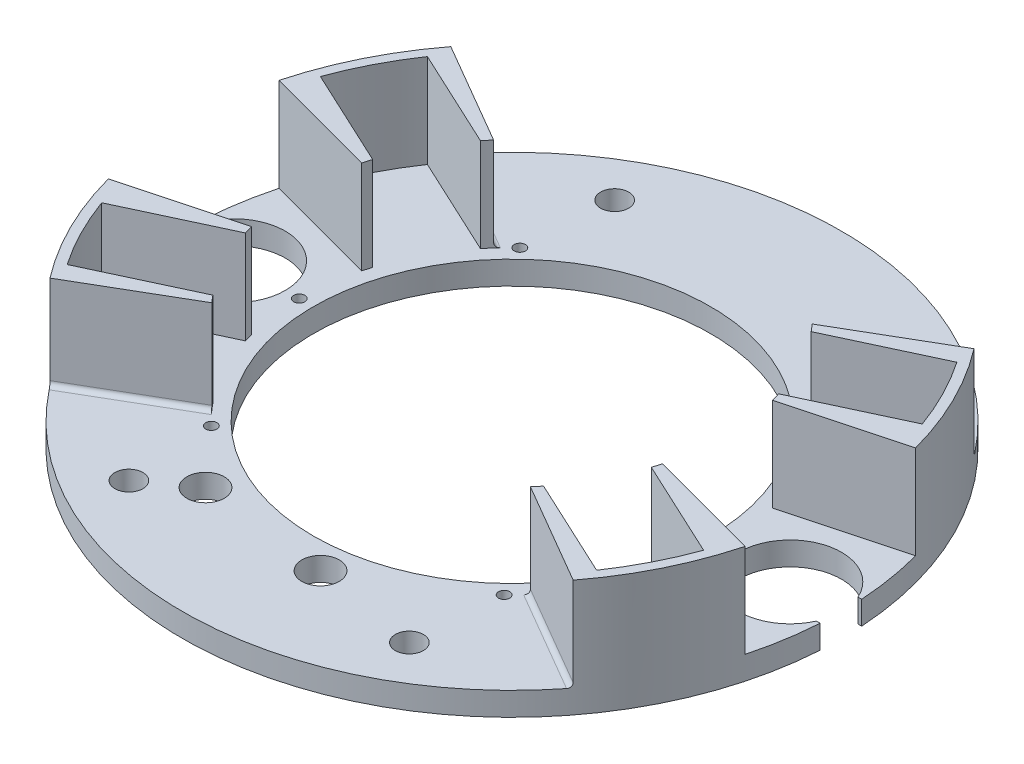
SolidWorks part; units mm, degrees
ref_plane "Front Plane" through (0, 0, 0) normal (0, 0, 1) x (1, 0, 0)
ref_plane "Top Plane" through (0, 0, 0) normal (0, 1, 0) x (1, 0, 0)
ref_plane "Right Plane" through (0, 0, 0) normal (1, 0, 0) x (0, 0, -1)
sketch "Sketch1" plane through (0, 0, 0) normal (0, 1, 0) x (1, 0, 0)
  circle A0 centre (0, 0) radius 53.975
  circle A1 centre (0, 0) radius 89.535
  dimension "D1" = 107.95
  dimension "D2" = 35.56
extrude "Base " add sketch "Sketch1" along normal blind 6.35
sketch "Sketch2" plane through (0, 6.35, 0) normal (0, 1, 0) x (1, 0, 0)
  line L0 (0, 0) -> (0, 53.975) construction
  line L1 (0, 0) -> (75.565, 0) construction
  line L2 (88.3404, 5.6524) -> (89.3564, 5.6524)
  line L3 (88.3404, -5.6524) -> (89.3564, -5.6524)
  circle A0 centre (0, 0) radius 53.975 construction
  circle A1 centre (0, 0) radius 89.535 construction
  circle A2 centre (0, 0) radius 89.535
  circle A3 centre (0, 0) radius 53.975
  arc A4 (88.3404, 5.6524) -> (88.3404, -5.6524) centre (75.565, 0) ccw
  dimension "D2" = 27.94
  dimension "D1" = 1.016
extrude "Noce Cone Pyros " cut sketch "Sketch2" against normal up to surface (6.35 mm away) contours A4 region at (75.6474, 6.35, 0) up to face at (0, 0, 89.535)
mirror "Nose Cone Pyro mirror " about plane through (0, 0, 0) normal (1, 0, 0) of "Noce Cone Pyros "
sketch "Sketch3" plane through (0, 6.35, 0) normal (0, 1, 0) x (1, 0, 0)
  line L0 (0, 0) -> (0, 53.975) construction
  line L1 (52.1358, 13.9698) -> (86.4842, 23.1734)
  line L2 (0, 0) -> (53.975, 0) construction
  line L3 (44.9222, 36.347) -> (74.256, 50.0256)
  line L4 (43.2815, 38.286) -> (71.074, 54.4518)
  line L5 (54.8014, 17.1318) -> (81.7661, 29.7057)
  circle A0 centre (0, 0) radius 53.975 construction
  circle A1 centre (0, 0) radius 89.535 construction
  circle A2 centre (0, 0) radius 89.535
  circle A3 centre (0, 0) radius 53.975
  circle A4 centre (0, 0) radius 86.995
  circle A5 centre (0, 0) radius 57.785
  arc A7 (-89.535, 0) -> (89.535, 0) centre (0, 0) ccw construction
  dimension "D1" = 15
  dimension "D2" = 90
  dimension "D3" = 21.59
  dimension "D5" = 5.185
  dimension "D7" = 10
  dimension "D8" = 2.54
  dimension "D4" = 2.54
  dimension "D6" = 3.81
extrude "Battery 1 Holder " add sketch "Sketch3" along normal blind 25.4 contours A4 L3 L4 | A5 L3 A4 L4 | A4 L1 L3 | L1 A4 L5 region at (71.5669, 6.35, -21.982) region at (79.9182, 6.35, -36.5031) region at (58.8023, 6.35, -44.9995) region at (71.5588, 6.35, -51.6651)
mirror "Batery 2 Holder " about plane through (0, 0, 0) normal (0, 0, 1) of "Battery 1 Holder "
mirror "Battery 3 Holder " about plane through (0, 0, 0) normal (1, 0, 0) of "Battery 1 Holder "
mirror "Battery 4 Holder " about plane through (0, 0, 0) normal (1, 0, 0) of "Batery 2 Holder "
sketch "Sketch4" plane through (0, 6.35, 0) normal (0, 1, 0) x (1, 0, 0)
  line L0 (0, 0) -> (0, -63.5) construction
  line L1 (0, 0) -> (38.1, 65.9911) construction
  circle A0 centre (0, 0) radius 53.975 construction
  circle A1 centre (38.1, 65.9911) radius 3.81
  dimension "D3" = 7.62
  dimension "D1" = 30
  dimension "D2" = 76.2
extrude "Bolt Hole " cut sketch "Sketch4" against normal up to surface (6.35 mm away) up to face at (0, 0, 53.975)
mirror "Bolt Hole 2 " about plane through (0, 0, 0) normal (0, 0, 1) of "Bolt Hole "
mirror "Bolt Hole 3 " about plane through (0, 0, 0) normal (1, 0, 0) of "Bolt Hole "
mirror "Bolt Hole 4 " about plane through (0, 0, 0) normal (1, 0, 0) of "Bolt Hole 2 "
sketch "Sketch11" plane through (0, 0, 0) normal (0, -1, 0) x (1, 0, 0)
  line L0 (0, 0) -> (9.1284, 61.146) construction
  line L1 (0, 0) -> (-26.0597, 57.2093) construction
  line L2 (0, 0) -> (-61.595, 0) construction
  circle A0 centre (9.1284, 61.146) radius 5.08
  circle A1 centre (-26.0597, 57.2093) radius 5.08
  arc A2 (-88.3404, -5.6524) -> (-88.3404, 5.6524) centre (-75.565, 0) ccw construction
  dimension "D4" = 10.16
  dimension "D5" = 10.16
  dimension "D1" = 62.865
  dimension "D2" = 61.8236
  dimension "D3" = 35.4076
  dimension "D6" = 65.51
extrude "Cut-Extrude2" cut sketch "Sketch11" against normal up to surface (6.35 mm away) up to face at (-38.1, 6.35, 62.1811)
sketch "Sketch13" plane through (0, 0, 0) normal (0, -1, 0) x (1, 0, 0)
  line L0 (0, 0) -> (0, 41.91) construction
  line L1 (0, 41.91) -> (39.7764, 41.91) construction
  line L2 (0, 41.91) -> (-39.7764, 41.91) construction
  circle A2 centre (39.7764, 41.91) radius 3.175
  circle A3 centre (-39.7764, 41.91) radius 3.175
  dimension "D4" = 6.35
  dimension "D5" = 6.35
  dimension "D1" = 79.5528
  dimension "D2" = 41.91
  dimension "D3" = 39.7764
extrude "Cut-Extrude3" cut sketch "Sketch13" against normal blind 3.175
sketch "Sketch14" plane through (0, 3.175, 0) normal (0, -1, 0) x (1, 0, 0)
  circle A0 centre (39.7764, 41.91) radius 1.524
  circle A1 centre (-39.7764, 41.91) radius 1.524
  dimension "D1" = 3.048
  dimension "D2" = 3.048
extrude "Cut-Extrude4" cut sketch "Sketch14" against normal up to surface (3.175 mm away) up to face at (9.1284, 6.35, 66.226)
mirror "Mirror1" about plane through (0, 0, 0) normal (0, 0, 1) of "Cut-Extrude3", "Cut-Extrude4"
sketch "Sketch15" plane through (0, 0, 0) normal (0, -1, 0) x (1, 0, 0)
  line L0 (0, 0) -> (57.785, 0) construction
  circle A0 centre (57.785, 0) radius 1.524
  circle A2 centre (0, 0) radius 53.975 construction
  dimension "D1" = 3.048
  dimension "D2" = 57.785
fillet "Fillet3" radius 1.27 4 edges at (57.1778, 6.35, 46.3689) (-57.1778, 6.35, 46.3689) (-57.1778, 6.35, -46.3689) (57.1778, 6.35, -46.3689)
extrude "Cut-Extrude5" cut sketch "Sketch15" against normal up to surface (6.35 mm away) up to face at (39.7764, 6.35, -40.386)
mirror "Mirror2" about plane through (0, 0, 0) normal (1, 0, 0) of "Cut-Extrude5"
equation "\"0..800in\"=0.1"
